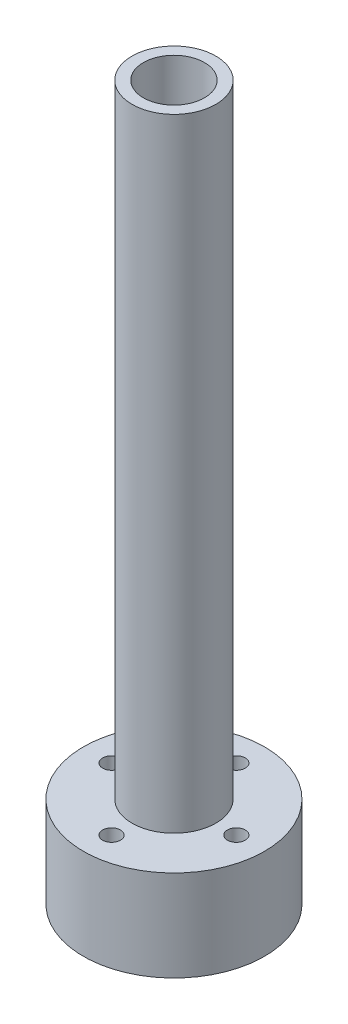
SolidWorks part; units mm, degrees
ref_plane "Front Plane" through (0, 0, 0) normal (0, 0, 1) x (1, 0, 0)
ref_plane "Top Plane" through (0, 0, 0) normal (0, 1, 0) x (1, 0, 0)
ref_plane "Right Plane" through (0, 0, 0) normal (1, 0, 0) x (0, 0, -1)
sketch "Sketch1" plane through (0, 0, 0) normal (0, 1, 0) x (1, 0, 0)
  circle A0 centre (0, 0) radius 10.16
  circle A1 centre (7, 0) radius 1
  circle A2 centre (0, -7) radius 1
  circle A3 centre (-7, 0) radius 1
  circle A4 centre (0, 7) radius 1
  point P14 (0, 0)
  dimension "D1" = 20.32
  dimension "D2" = 2
  dimension "D3" = 7
  dimension "D4" = 4
extrude "Boss-Extrude1" add sketch "Sketch1" along normal blind 19.05
sketch "Sketch2" plane through (0, 19.05, 0) normal (0, 1, 0) x (1, 0, 0)
  circle A0 centre (0, 0) radius 4.699
  dimension "D1" = 9.398
extrude "Boss-Extrude2" add sketch "Sketch2" along normal blind 88.9 from surface starting at face at (0, 0, 10.16)
sketch "Sketch3" plane through (0, 88.9, 0) normal (0, 1, 0) x (1, 0, 0)
  circle A0 centre (0, 0) radius 3.429
  dimension "D1" = 6.858
extrude "Cut-Extrude1" cut sketch "Sketch3" against normal through all
sketch "Sketch4" plane through (0, 0, 0) normal (0, -1, 0) x (1, 0, 0)
  circle A1 centre (0, 0) radius 10.16
  circle A2 centre (0, 0) radius 10.16
  dimension "D1" = 0
extrude "Cut-Extrude2" cut sketch "Sketch4" against normal blind 8.842
equation "\"D3@Sketch1\"=7MM"
equation "\"D2@Sketch1\"=2MM"
equation "\"tightTol\" = 0.005in"
equation "\"normTol\" = 0.01in"
equation "\"looseTol\" = 0.02in"
equation "\"D1@Sketch2\"=0.375000-\"tightTol\""
equation "\"D1@Sketch3\"=1/4+\"looseTol\""
equation "\"D1@Cut-Extrude2\"= 15.7mm - 0.25 - \"looseTol\""
